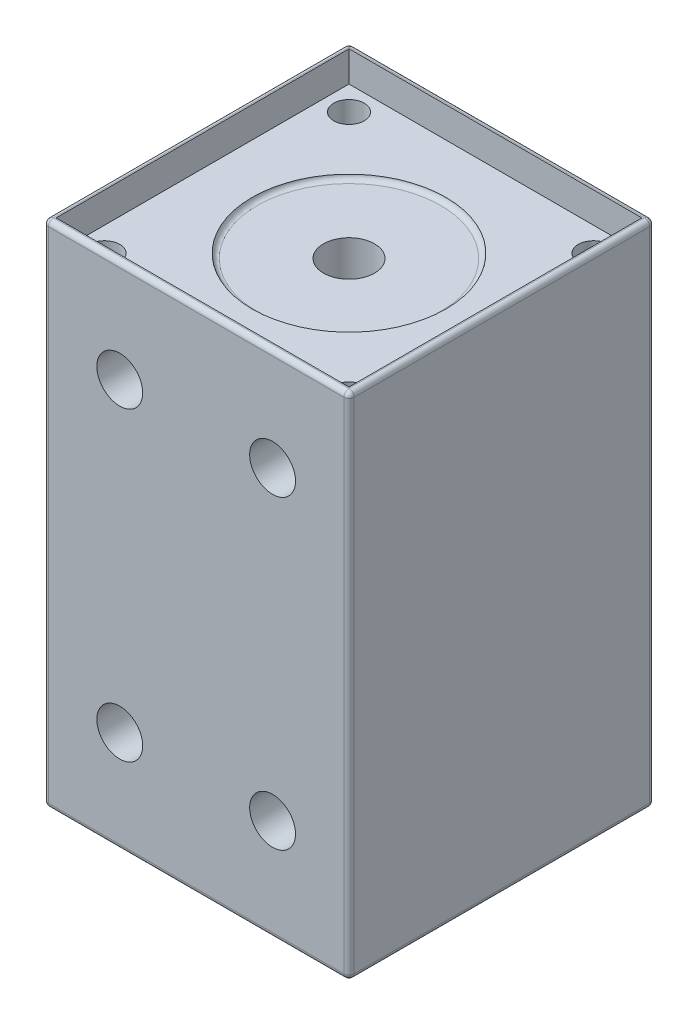
SolidWorks part; units mm, degrees
material "3.0255 (EN-AW 1350A)"
ref_plane "Płaszczyzna przednia" through (0, 0, 0) normal (0, 0, 1) x (1, 0, 0)
ref_plane "Płaszczyzna górna" through (0, 0, 0) normal (0, 1, 0) x (1, 0, 0)
ref_plane "Płaszczyzna prawa" through (0, 0, 0) normal (1, 0, 0) x (0, 0, -1)
sketch "Szkic1" plane through (0, 0, 0) normal (0, 1, 0) x (1, 0, 0)
  line L1 (30, -30) -> (-30, -30)
  line L2 (30, -30) -> (30, 30)
  line L3 (30, 30) -> (-30, 30)
  line L4 (-30, -30) -> (-30, 30)
  line L5 (30, -30) -> (-30, 30) construction
  line L6 (30, 30) -> (-30, -30) construction
  point P0 (0, 0)
  dimension "D1" = 60
  dimension "D2" = 60
extrude "Dodanie-wyciągnięcie1" add sketch "Szkic1" along normal blind 100
sketch "Szkic2" plane through (0, 100, 0) normal (0, 1, 0) x (1, 0, 0)
  line L1 (-28.75, -28.75) -> (28.75, -28.75)
  line L2 (-28.75, -28.75) -> (-28.75, 28.75)
  line L3 (-28.75, 28.75) -> (28.75, 28.75)
  line L4 (28.75, -28.75) -> (28.75, 28.75)
  line L5 (-28.75, -28.75) -> (28.75, 28.75) construction
  line L6 (-28.75, 28.75) -> (28.75, -28.75) construction
  point P0 (0, 0)
  dimension "D1" = 57.5
  dimension "D2" = 57.5
extrude "Wytnij-wyciągnięcie1" cut sketch "Szkic2" against normal blind 6
sketch "Szkic3" plane through (0, 94, 0) normal (0, 1, 0) x (1, 0, 0)
  circle A0 centre (0, 0) radius 5
  dimension "D1" = 10
extrude "Wytnij-wyciągnięcie2" cut sketch "Szkic3" against normal blind 24
sketch "Szkic4" plane through (0, 94, 0) normal (0, 1, 0) x (1, 0, 0)
  circle A0 centre (0, 0) radius 19
  dimension "D1" = 38
extrude "Wytnij-wyciągnięcie3" cut sketch "Szkic4" against normal blind 0.9
fillet "Zaokrąglenie1" radius 1 1 edges at (0, 93.1, 19)
sketch "Szkic5" plane through (0, 94, 0) normal (0, 1, 0) x (1, 0, 0)
  line L2 (0, -33) -> (0, 33) construction
  line L3 (-33, 0) -> (33, 0) construction
  line L4 (30, 30) -> (-30, 30) construction
  line L5 (-30, 30) -> (-30, -30) construction
  circle A0 centre (-24, 24) radius 3
  circle A1 centre (24, 24) radius 3
  circle A2 centre (24, -24) radius 3
  circle A3 centre (-24, -24) radius 3
  dimension "D1" = 6
  dimension "D2" = 6
  dimension "D3" = 6
hole_wizard "Otwory ustalające Ø6.0mm1" positions "Szkic6" profile "Szkic7" hole size "Ø6.0" standard "ISO" end condition through all
sketch "Szkic6" plane through (0, 94, 0) normal (0, 1, 0) x (1, 0, 0)
  point P0 (-24, 24)
  point P3 (24, 24)
  point P6 (24, -24)
  point P9 (-24, -24)
sketch "Szkic7" plane through (-24, 94, -24) normal (1, 0, 0) x (0, 0, 1)
  line L0 (0, 0) -> (0, 94)
  line L1 (0, 94) -> (3, 94)
  line L2 (3, 94) -> (3, 0)
  line L5 (3, 0) -> (0, 0)
  line L11 (0, -6.35) -> (0, 107.95) construction
  dimension "Średnica otworu na wylot" = 6
  dimension "Głębokość otworu na wylot" = 94
sketch "Szkic8" plane through (0, 0, 0) normal (0, -1, 0) x (1, 0, 0)
  circle A0 centre (0, 0) radius 21
  dimension "D1" = 42
extrude "Wytnij-wyciągnięcie5" cut sketch "Szkic8" against normal blind 70
fillet "Zaokrąglenie2" radius 1 12 edges at (0, 100, 30) (30, 50, 30) (30, 100, 0) (-30, 100, 0) (-30, 50, 30) (30, 50, -30) (0, 100, -30) (-30, 50, -30) (0, 0, 30) (30, 0, 0) (-30, 0, 0) (0, 0, -30)
sketch "Szkic9" plane through (0, 0, -30) normal (0, 0, -1) x (-1, 0, 0)
  line L0 (-15, 116.6784) -> (-15, -11.4858) construction
  line L1 (-60.8132, 20) -> (51.3545, 20) construction
  line L2 (-71.606, 80) -> (65.8091, 80) construction
  line L3 (15, 116.6784) -> (15, -11.4858) construction
  line L4 (-29, 100) -> (29, 100) construction
  line L5 (30, 99) -> (30, 1) construction
  dimension "D1" = 60
  dimension "D2" = 30
  dimension "D3" = 20
  dimension "D4" = 15
hole_wizard "Otwór pod śrubę M81" positions "Szkic10" profile "Szkic11" hole size "M8" standard "ISO"
sketch "Szkic10" plane through (0, 0, -30) normal (0, 0, -1) x (-1, 0, 0)
  line L0 (-15, 116.6784) -> (-15, -11.4858) construction
  line L1 (-71.606, 80) -> (65.8091, 80) construction
  line L2 (15, 116.6784) -> (15, -11.4858) construction
  line L3 (-60.8132, 20) -> (51.3545, 20) construction
  point P0 (-15, 80)
  point P6 (15, 80)
  point P10 (15, 20)
  point P14 (-15, 20)
sketch "Szkic11" plane through (15, 80, -30) normal (1, 0, 0) x (0, 1, 0)
  line L0 (0, 0) -> (0, 12.7039)
  line L1 (0, 12.7039) -> (4.5, 10)
  line L2 (4.5, 10) -> (4.5, 0)
  line L5 (4.5, 0) -> (0, 0)
  line L10 (0, 12.7039) -> (-4.5, 10) construction
  line L11 (0, -6.35) -> (0, 107.95) construction
  dimension "Średnica otworu" = 9
  dimension "Głębokość otworu" = 10
  dimension "Kąt wiertła" = 118
mirror "Lustro1" about plane through (0, 0, 0) normal (0, 0, 1) of "Otwór pod śrubę M81"
